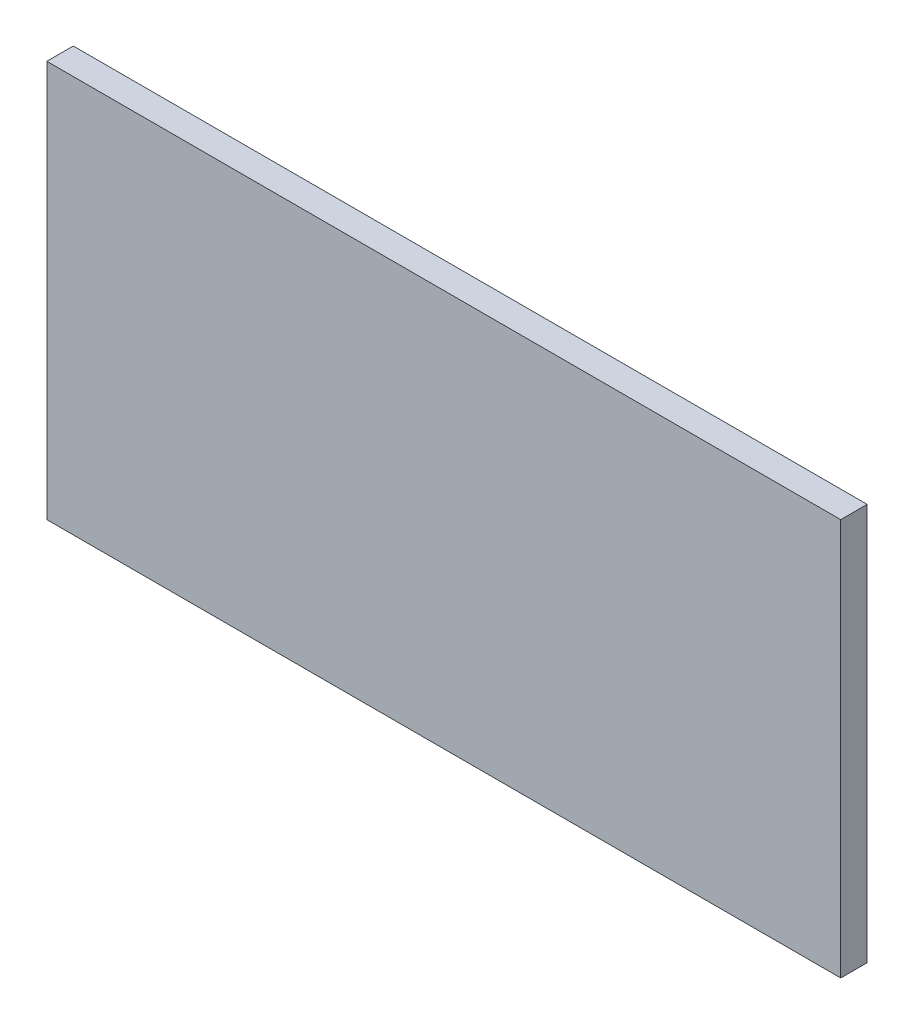
SolidWorks part; units mm, degrees
material "Лист 6,0 ГОСТ 19903-2015 / Ст3сп ГОСТ 14637-89"
ref_plane "Спереди" through (0, 0, 0) normal (0, 0, 1) x (1, 0, 0)
ref_plane "Сверху" through (0, 0, 0) normal (0, 1, 0) x (1, 0, 0)
ref_plane "Справа" through (0, 0, 0) normal (1, 0, 0) x (0, 0, -1)
sketch "Эскиз1" plane through (0, 0, 0) normal (0, 0, 1) x (1, 0, 0)
  line L1 (-90, -45) -> (90, -45)
  line L2 (-90, -45) -> (-90, 45)
  line L3 (-90, 45) -> (90, 45)
  line L4 (90, -45) -> (90, 45)
base flange "Базовая кромка1" sketch "Эскиз1" thickness 6 reverse thickness direction no parameters "D1"=6
sketch "Сгиб-Линии1" [suppressed] plane through (0, 0, 0) normal (0, 1, 0) x (1, 0, 0)
sketch "Граничная рамка1" [suppressed] plane through (0, 0, 0) normal (0, 1, 0) x (1, 0, 0)
sheet metal parameters "Листовой металл30" thickness 6 parameters "D1"=6
flat pattern "Развертка30" [suppressed]
sketch "Сгиб-Линии2" plane through (0, 0, 0) normal (0, 1, 0) x (1, 0, 0)
sketch3d "Граничная рамка2" [suppressed]
  line L0 (90, -45, 0) -> (-90, -45, 0) construction
  line L1 (90, 45, 0) -> (-90, 45, 0) construction
  line L2 (90, -45, 0) -> (90, 45, 0) construction
  line L3 (-90, -45, 0) -> (-90, 45, 0) construction
